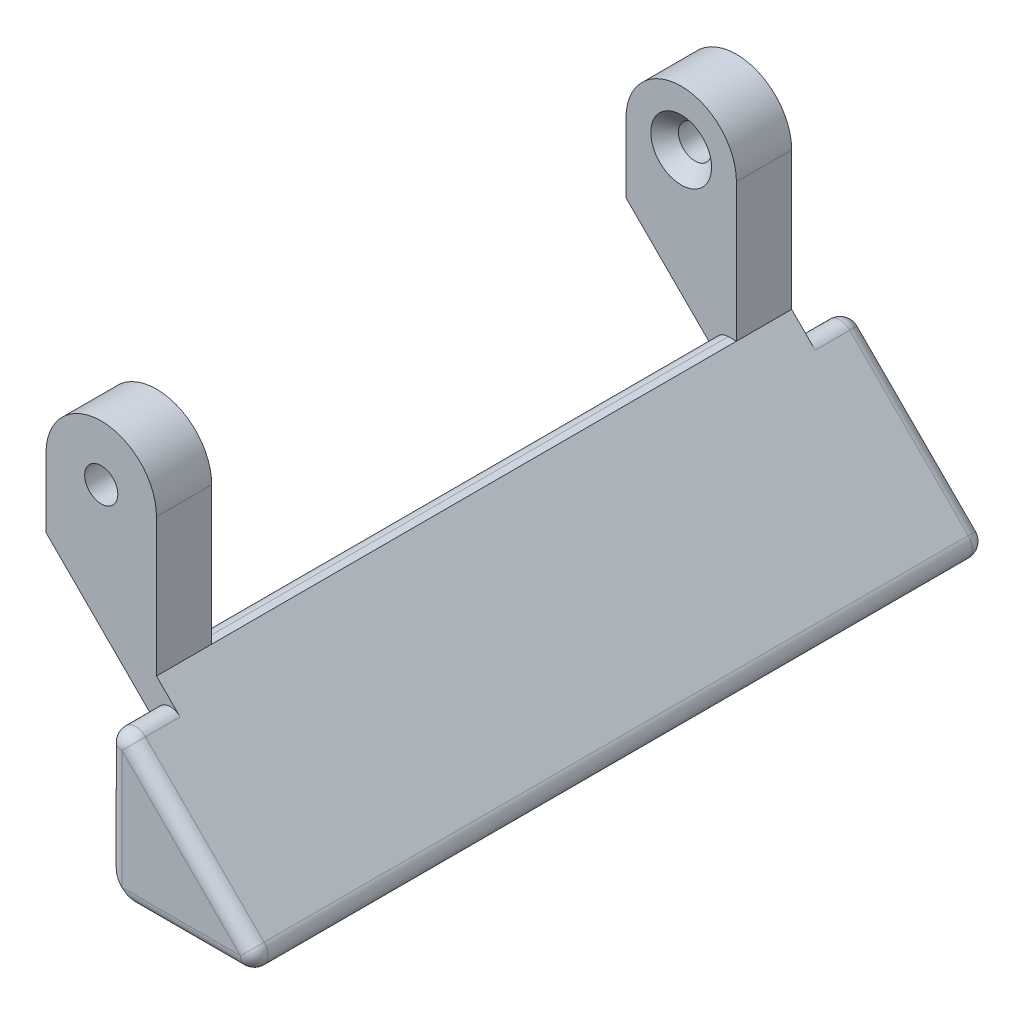
SolidWorks part; units mm, degrees
material "Liga 1060"
ref_plane "Plano frontal" through (0, 0, 0) normal (0, 0, 1) x (1, 0, 0)
ref_plane "Plano superior" through (0, 0, 0) normal (0, 1, 0) x (1, 0, 0)
ref_plane "Plano direito" through (0, 0, 0) normal (1, 0, 0) x (0, 0, -1)
sketch "Esboço1" plane through (0, 0, 0) normal (0, 0, 1) x (1, 0, 0)
  line L0 (0, 0) -> (0, 22)
  line L1 (0, 0) -> (20, 0)
  line L2 (20, 0) -> (8, 12)
  line L3 (8, 12) -> (8, 22)
  arc A0 (8, 22) -> (0, 22) centre (4, 22) ccw
  dimension "D1" = 20
  dimension "D2" = 22
  dimension "D3" = 45
  dimension "D4" = 8
extrude "Ressalto-extrusão1" add sketch "Esboço1" along normal blind 53
sketch "Esboço2" plane through (0, 0, 0) normal (-1, 0, 0) x (0, 0, 1)
  line L0 (0, 0) -> (0, 11)
  line L1 (0, 22) -> (0, 0) construction
  line L2 (0, 11) -> (21, 11)
  line L4 (53, 0) -> (0, 0) construction
  line L5 (21, 0) -> (0, 0)
  line L6 (21, 0) -> (32, 0)
  line L7 (32, 0) -> (53, 0)
  line L8 (53, 22) -> (53, 0) construction
  line L9 (53, 0) -> (53, 11)
  line L10 (53, 11) -> (32, 11)
  line L12 (21, 11) -> (32, 11)
  dimension "D1" = 11
  dimension "D2" = 21
  dimension "D3" = 21
extrude "Corte-extrusão1" cut sketch "Esboço2" against normal blind 8
sketch "Esboço3" plane through (0, 0, 0) normal (-1, 0, 0) x (0, 0, 1)
  line L0 (0, 0) -> (3.5, 0)
  line L2 (3.5, 0) -> (3.5, 26)
  line L3 (53, 26) -> (0, 26) construction
  line L4 (3.5, 26) -> (0, 26)
  line L5 (0, 26) -> (0, 0)
  line L6 (53, 0) -> (49.5, 0)
  line L7 (53, 22) -> (53, 11) construction
  line L8 (49.5, 0) -> (49.5, 26)
  line L9 (49.5, 26) -> (53, 26)
  line L10 (53, 26) -> (53, 0)
  line L12 (0, 0) -> (53, 0) construction
  line L13 (0, 22) -> (0, 11) construction
  dimension "D1" = 3.5
  dimension "D2" = 3.5
extrude "Corte-extrusão2" cut sketch "Esboço3" against normal up to surface (8 mm away) up to face at (8, 17, 26.5)
chamfer "Chanfro1" distance 2 angle 45 1 edges at (8, 0, 26.5)
chamfer "Chanfro2" distance 2 angle 45 1 edges at (8, 11, 26.5)
sketch "Esboço6" plane through (0, 0, 3.5) normal (0, 0, -1) x (-1, 0, 0)
  line L0 (-8, 12) -> (0, 20)
  line L1 (0, 11) -> (0, 22) construction
  line L2 (0, 20) -> (0, 22)
  line L3 (-8, 22) -> (-8, 12)
  line L4 (-8, 9) -> (-6, 11) construction
  line L5 (-8, 12) -> (-8, 22) construction
  arc A0 (0, 22) -> (-8, 22) centre (-4, 22) ccw
extrude "Corte-extrusão4" cut sketch "Esboço6" against normal offset from surface (38 mm away) 4 from offset 4 contours L0 L2 A0 L3 up to face at (5, 15.1667, 49.5) offset against normal yes
sketch "Esboço8" plane through (8, 0, 0) normal (1, 0, 0) x (0, 0, -1)
  line L0 (-45.5, 12) -> (-7.5, 12)
  line L1 (-7.5, 12) -> (-7.5, 20)
  line L2 (-7.5, 20) -> (-45.5, 20)
  line L3 (-45.5, 20) -> (-45.5, 12)
  line L4 (-53, 0) -> (0, 0) construction
  dimension "D1" = 12
extrude "Corte-extrusão5" cut sketch "Esboço8" against normal through all both and the other way through all
sketch "Esboço9" plane through (0, 0, 7.5) normal (0, 0, 1) x (1, 0, 0)
  line L0 (8, 22) -> (0, 22) construction
  point P4 (4, 22)
sketch "Esboço10" plane through (0, 0, 45.5) normal (0, 0, -1) x (-1, 0, 0)
  line L0 (-8, 22) -> (0, 22) construction
  point P4 (-4, 22)
hole_wizard "Escareado para parafuso com cabeça escareada chata de M21" positions "3DSketch1" profile "Esboço11" countersink size "M2" standard "ISO" end condition through all
sketch3d "3DSketch1"
  point P0 (4, 22, 45.5)
  point P3 (4, 22, 7.5)
sketch "Esboço11" plane through (4, 22, 45.5) normal (1, 0, 0) x (0, 1, 0)
  line L0 (0, 0) -> (0, 7.5)
  line L1 (0, 7.5) -> (1.2, 7.5)
  line L2 (1.2, 7.5) -> (1.2, 1)
  line L3 (1.2, 1) -> (2.2, 0)
  line L5 (2.2, 0) -> (0, 0)
  line L6 (-1.2, 1) -> (-2.2, 0) construction
  line L11 (0, -6.35) -> (0, 107.95) construction
  dimension "Thru Hole Dia." = 2.4
  dimension "Thru Hole Depth" = 7.5
  dimension "Near C'Sink Dia." = 4.4
  dimension "Near C'Sink Angle" = 90
sketch "Esboço12" plane through (0, 0, 49.5) normal (0, 0, 1) x (1, 0, 0)
  line L0 (0, 11) -> (6, 11)
  line L3 (6, 11) -> (0, 17)
  line L4 (6, 11) -> (0, 11) construction
  line L5 (0, 17) -> (0, 11)
  line L7 (6, 11) -> (0, 11) construction
  dimension "D2" = 45
extrude "Corte-extrusão6" cut sketch "Esboço12" against normal through all
fillet "Filete1" radius 1 1 edges at (5, 12, 26.5)
fillet "Filete3" radius 1 5 edges at (20, 0, 26.5) (14, 6, 0) (15, 0, 0) (14, 6, 53) (15, 0, 53) tangent propagation no
fillet "Filete4" radius 1 6 edges at (8, 6.2929, 0) (8, 11.5858, 0.2929) (8, 6.2929, 53) (8, 11.5858, 52.7071) (8, 12, 2.25) (8, 12, 50.75)
